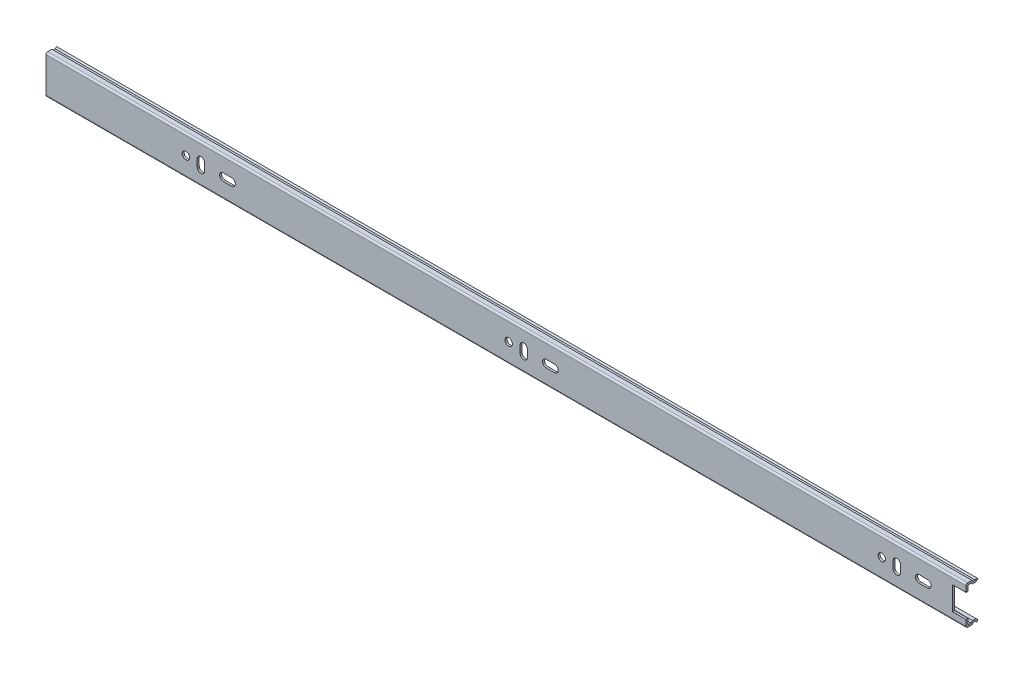
SolidWorks part; units mm, degrees
ref_plane "Спереди" through (0, 0, 0) normal (0, 0, 1) x (1, 0, 0)
ref_plane "Сверху" through (0, 0, 0) normal (0, 1, 0) x (1, 0, 0)
ref_plane "Справа" through (0, 0, 0) normal (1, 0, 0) x (0, 0, -1)
sketch "Эскиз1" plane through (0, 0, 0) normal (1, 0, 0) x (0, 0, -1)
  line L0 (0, 10.5) -> (0, -10.5)
  line L1 (-12.4481, 0) -> (26.4522, 0) construction
  line L2 (3.5733, 11.5) -> (1, 11.5)
  line L3 (4.3714, 10.7019) -> (3.5733, 11.5)
  line L4 (5.5019, 10.7019) -> (4.3714, 10.7019)
  line L5 (6.3, -11.5) -> (5.5019, -10.7019)
  line L6 (5.5019, -10.7019) -> (4.3714, -10.7019)
  line L7 (4.3714, -10.7019) -> (3.5733, -11.5)
  line L8 (3.5733, -11.5) -> (1, -11.5)
  line L9 (6.3, 11.5) -> (5.5019, 10.7019)
  arc A0 (0, 10.5) -> (1, 11.5) centre (1, 10.5) cw
  arc A2 (0, -10.5) -> (1, -11.5) centre (1, -10.5) ccw
  point P0 (0, -11.5)
  point P1 (0, 11.5)
  point P12 (0, 0)
  point P20 (0, 0)
extrude "Вытянуть-Тонкостенный3" add sketch "Эскиз1" along normal blind 550 thin thin type one direction wall 1.2
sketch "Эскиз2" plane through (0, 0, 0) normal (0, 0, 1) x (1, 0, 0)
  line L0 (550, -10.5) -> (550, 10.5) construction
  line L1 (550, 7) -> (541.8, 7)
  line L2 (550, 7) -> (550, -7)
  line L3 (550, -7) -> (541.8, -7)
  line L4 (541.8, 7) -> (541.8, -7)
  line L5 (522, 2.2) -> (527, 2.2)
  line L6 (522, -2.2) -> (527, -2.2)
  line L7 (506.4, 1.7796) -> (506.4, -2.5)
  line L8 (510.8, -2.5) -> (510.8, 1.7796)
  line L9 (283.4, 1.7796) -> (283.4, -2.5)
  line L10 (287.8, -2.5) -> (287.8, 1.7796)
  line L11 (299, -2.2) -> (304, -2.2)
  line L12 (299, 2.2) -> (304, 2.2)
  line L13 (94.8, -2.5) -> (94.8, 1.7796)
  line L14 (90.4, 1.7796) -> (90.4, -2.5)
  line L15 (106, 2.2) -> (111, 2.2)
  line L16 (106, -2.2) -> (111, -2.2)
  circle A0 centre (499.6, 0) radius 2.2
  arc A1 (522, 2.2) -> (522, -2.2) centre (522, 0) ccw
  arc A2 (527, 2.2) -> (527, -2.2) centre (527, 0) cw
  arc A3 (506.4, -2.5) -> (510.8, -2.5) centre (508.6, -2.5) ccw
  arc A4 (510.8, 1.7796) -> (506.4, 1.7796) centre (508.6, 1.7796) ccw
  arc A5 (283.4, -2.5) -> (287.8, -2.5) centre (285.6, -2.5) ccw
  circle A6 centre (276.6, 0) radius 2.2
  arc A7 (287.8, 1.7796) -> (283.4, 1.7796) centre (285.6, 1.7796) ccw
  arc A8 (299, 2.2) -> (299, -2.2) centre (299, 0) ccw
  arc A9 (304, 2.2) -> (304, -2.2) centre (304, 0) cw
  arc A10 (90.4, -2.5) -> (94.8, -2.5) centre (92.6, -2.5) ccw
  arc A11 (94.8, 1.7796) -> (90.4, 1.7796) centre (92.6, 1.7796) ccw
  circle A12 centre (83.6, 0) radius 2.2
  arc A13 (111, 2.2) -> (111, -2.2) centre (111, 0) cw
  arc A14 (106, 2.2) -> (106, -2.2) centre (106, 0) ccw
extrude "Вырез-Вытянуть1" cut sketch "Эскиз2" against normal through all
